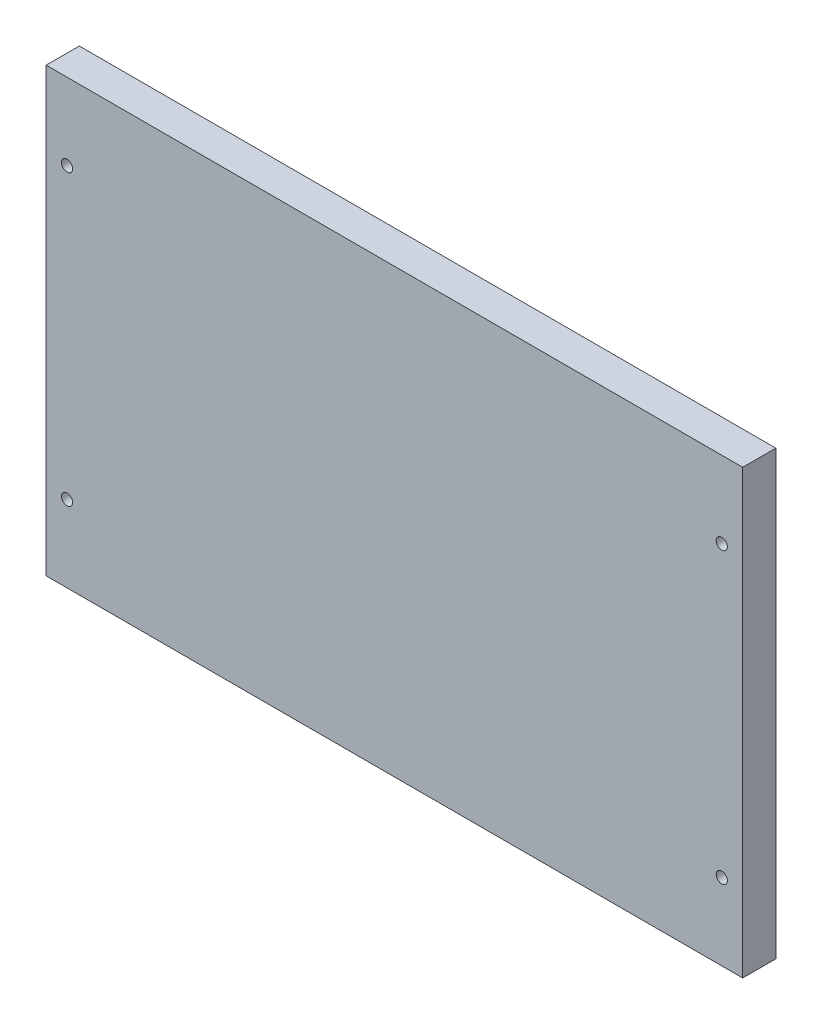
SolidWorks part; units mm, degrees
ref_plane "Front Plane" through (0, 0, 0) normal (0, 0, 1) x (1, 0, 0)
ref_plane "Top Plane" through (0, 0, 0) normal (0, 1, 0) x (1, 0, 0)
ref_plane "Right Plane" through (0, 0, 0) normal (1, 0, 0) x (0, 0, -1)
sketch "Sketch1" plane through (0, 0, 0) normal (0, 0, 1) x (1, 0, 0)
  line L1 (0, 0) -> (200, 0)
  line L2 (0, 0) -> (0, 127)
  line L3 (0, 127) -> (200, 127)
  line L4 (200, 0) -> (200, 127)
  circle A3 centre (6, 105) radius 1.6
  circle A4 centre (6, 22) radius 1.6
  circle A5 centre (194, 22) radius 1.6
  circle A6 centre (194, 105) radius 1.6
  dimension "D11" = 3.2
  dimension "D14" = 3.2
  dimension "D17" = 3.2
  dimension "D22" = 3.2
  dimension "D1" = 127
  dimension "D2" = 200
  dimension "D12" = 6
  dimension "D13" = 22
  dimension "D15" = 6
  dimension "D16" = 22
  dimension "D18" = 6
  dimension "D19" = 22
  dimension "D20" = 6
  dimension "D21" = 22
extrude "Wall" add sketch "Sketch1" along normal blind 9.525
sketch "Sketch2" [suppressed] plane through (0, 0, 9.525) normal (0, 0, 1) x (1, 0, 0)
  line L0 (100, 127) -> (100, 98.425) construction
  line L1 (200, 127) -> (0, 127) construction
  line L2 (100, 98.425) -> (66.6667, 98.425) construction
  line L3 (100, 98.425) -> (133.3333, 98.425) construction
  line L4 (0, 127) -> (0, 0) construction
  circle A0 centre (100, 98.425) radius 3.9687
  circle A1 centre (66.6667, 98.425) radius 3.9688
  circle A2 centre (133.3333, 98.425) radius 3.9687
  dimension "D2" = 7.9375
  dimension "D1" = 28.575
  dimension "D3" = 66.6667
extrude "RodSupportCutouts" [suppressed] cut sketch "Sketch2" against normal up to next
sketch "Sketch3" [suppressed] plane through (0, 0, 9.525) normal (0, 0, 1) x (1, 0, 0)
  line L1 (25.4, 88.9) -> (174.6, 88.9)
  line L2 (25.4, 88.9) -> (25.4, 114.3)
  line L3 (25.4, 114.3) -> (174.6, 114.3)
  line L4 (174.6, 88.9) -> (174.6, 114.3)
  line L5 (25.4, 88.9) -> (174.6, 114.3) construction
  line L6 (25.4, 114.3) -> (174.6, 88.9) construction
  line L7 (200, 127) -> (0, 127) construction
  line L8 (0, 127) -> (0, 0) construction
  point P0 (100, 101.6)
  point P9 (100, 127)
  dimension "D1" = 25.4
  dimension "D2" = 25.4
  dimension "D3" = 25.4
extrude "CannulaLargeCutout" [suppressed] cut sketch "Sketch3" against normal up to next
sketch "Sketch4" [suppressed] plane through (0, 0, 9.525) normal (0, 0, 1) x (1, 0, 0)
  line L0 (6, 103.5) -> (194, 103.5) construction
  line L1 (6, 105) -> (6, 22) construction
  line L2 (194, 105) -> (194, 22) construction
  line L3 (200, 127) -> (0, 127) construction
  line L4 (0, 127) -> (0, 0) construction
  circle A0 centre (60, 103.5) radius 6.35
  circle A1 centre (20, 103.5) radius 6.35
  circle A2 centre (100, 103.5) radius 6.35
  circle A3 centre (140, 103.5) radius 6.35
  circle A4 centre (60, 63.5) radius 6.35
  circle A5 centre (100, 63.5) radius 6.35
  circle A6 centre (140, 63.5) radius 6.35
  circle A7 centre (60, 23.5) radius 6.35
  circle A8 centre (100, 23.5) radius 6.35
  circle A9 centre (140, 23.5) radius 6.35
  circle A10 centre (20, 63.5) radius 6.35
  circle A11 centre (20, 23.5) radius 6.35
  circle A12 centre (180, 103.5) radius 6.35
  circle A13 centre (180, 63.5) radius 6.35
  circle A14 centre (180, 23.5) radius 6.35
  point P42 (100, 127)
  point P45 (0, 63.5)
  dimension "D3" = 12.7
  dimension "D1" = 5
  dimension "D2" = 3
extrude "CannulaHoles" [suppressed] cut sketch "Sketch4" against normal up to next
equation "\"Length\"= 283mm"
equation "\"Width\"= 225mm"
equation "\"WallThickness\"= 12.5mm"
equation "\"UpperWaterJacketThickness\"= 28mm"
equation "\"SpacerHeight\"= 80.2mm"
equation "\"SpacerCornerWidth\"= 10mm"
equation "\"SpacerCornerHeight\"= 60.16mm"
equation "\"SpacerPegDiameter\"= 10mm"
equation "\"SpacerPegHeight\"= 10mm"
equation "\"TubingShort\"= 110mm"
equation "\"TubingLong\"= 175mm"
equation "\"PlateLength\"= 252mm"
equation "\"PlateWidth\"= 190mm"
equation "\"PlateHoleDiameter\"= 5.9mm"
equation "\"PlateHoleBottom\"= 2mm"
equation "\"PlateHoleSide\"= 1.55mm"
equation "\"PlateHoleSpacing\"= 3.1mm"
equation "\"PlateThickness\"= 1.55mm"
equation "\"ReservoirBottom\"= 12.5mm"
equation "\"ReservoirSupportWidth\"= 12mm"
equation "\"ReservoirSupportHeight\"= 15.1mm"
equation "\"ReservoirSupportPlacementHeight\"= 50mm"
equation "\"ReservoirHoleDiameter\"= 12.7mm"
equation "\"ReservoirHoleRight\"= 25mm"
equation "\"ReservoirHoleTop\"= \"ReservoirSupportPlacementHeight\""
equation "\"ReservoirHeight\"= 90mm"
equation "\"ReservoirPortBottom\"= 4mm"
equation "\"ReservoirPortTop\"= 10mm"
equation "\"ReservoirPortWidth\"= 101mm"
equation "\"CustomSpacerWallThickness\"= 0.375in"
equation "\"CustomSpacerHeight\"= 5in"
equation "\"CustomSpacerRodHoleHeight\"= .75in"
equation "\"CustomSpacerRodHoleDiameter\"= .3125in"
equation "\"ScrewBlockSide\"= 12mm"
equation "\"ScrewBlockUpperHeight\"= 16mm"
equation "\"ScrewBlockLowerHeight\"= 16mm"
equation "\"InternalLength\"= \"Length\" - ( 2 * \"WallThickness\" )"
equation "\"InternalWidth\"= \"Width\" - ( 2 * \"WallThickness\" )"
equation "\"CustomSpacerPegHeight\"= 1in"
equation "\"CustomSpacerScrewBore\"=3.2mm"
equation "\"CustomSpacerScrewDepth\"=10mm"
equation "\"D1@Sketch1\"=\"CustomSpacerHeight\""
equation "\"D2@Sketch1\"=\"InternalWidth\""
equation "\"D11@Sketch1\"=\"CustomSpacerScrewBore\""
equation "\"D12@Sketch1\"=\"ScrewBlockSide\"/2"
equation "\"D13@Sketch1\"=\"ScrewBlockUpperHeight\"+\"ScrewBlockSide\"/2"
equation "\"D14@Sketch1\"=\"CustomSpacerScrewBore\""
equation "\"D15@Sketch1\"=\"ScrewBlockSide\"/2"
equation "\"D16@Sketch1\"=\"ScrewBlockLowerHeight\"+\"ScrewBlockSide\"/2"
equation "\"D17@Sketch1\"=\"CustomSpacerScrewBore\""
equation "\"D18@Sketch1\"=\"ScrewBlockSide\"/2"
equation "\"D19@Sketch1\"=\"ScrewBlockUpperHeight\"+\"ScrewBlockSide\"/2"
equation "\"D20@Sketch1\"=\"ScrewBlockSide\"/2"
equation "\"D21@Sketch1\"=\"ScrewBlockLowerHeight\"+\"ScrewBlockSide\"/2"
equation "\"D22@Sketch1\"=\"CustomSpacerScrewBore\""
equation "\"D1@Wall\" = \"CustomSpacerWallThickness\""
equation "\"D1@Sketch2\"=\"CustomSpacerRodHoleHeight\" + \"CustomSpacerRodHoleDiameter\" +0.0625in"
equation "\"D2@Sketch2\"=\"CustomSpacerRodHoleDiameter\""
equation "\"D3@Sketch2\"=\"InternalWidth\" / 3"
equation "\"D1@Sketch3\"=1in"
